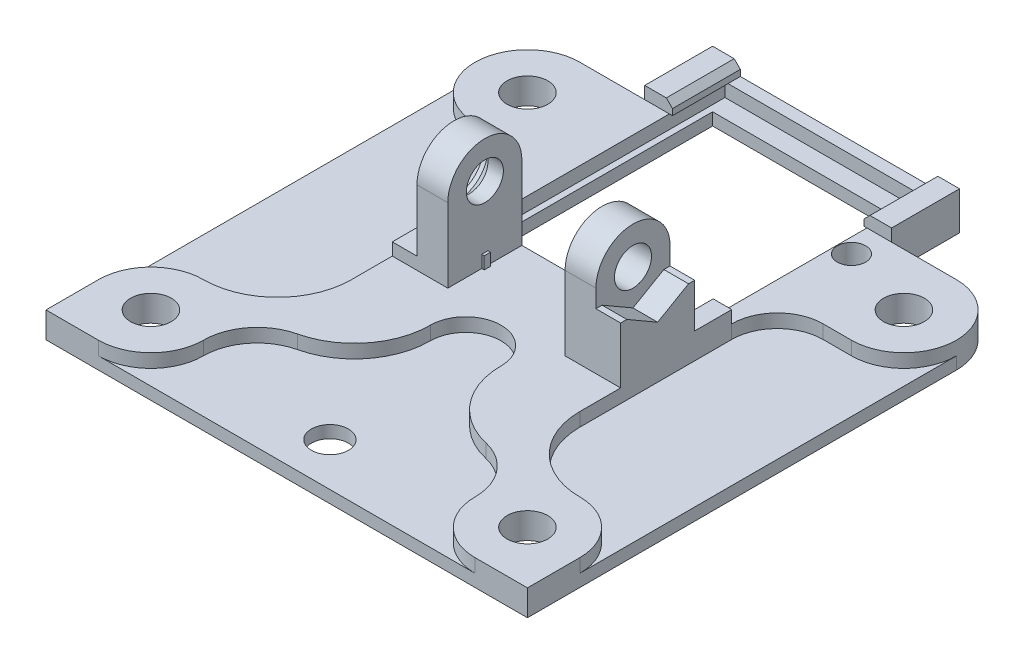
SolidWorks part; units mm, degrees
ref_plane "Front Plane" through (0, 0, 0) normal (0, 0, 1) x (1, 0, 0)
ref_plane "Top Plane" through (0, 0, 0) normal (0, 1, 0) x (1, 0, 0)
ref_plane "Right Plane" through (0, 0, 0) normal (1, 0, 0) x (0, 0, -1)
sketch "Sketch1" plane through (0, 0, 0) normal (0, 1, 0) x (1, 0, 0)
  line L0 (-19.5, 35.2) -> (-19.5, -19.5) construction
  line L1 (-19.5, 19.5) -> (19.5, 19.5)
  line L2 (-19.5, 19.5) -> (-19.5, -19.5)
  line L3 (-19.5, -19.5) -> (19.5, -19.5)
  line L4 (19.5, 19.5) -> (19.5, -19.5)
  line L5 (-19.5, 19.5) -> (19.5, -19.5) construction
  line L6 (-19.5, -19.5) -> (19.5, 19.5) construction
  line L7 (-19.5, -19.5) -> (19.5, -19.5) construction
  line L8 (0, -19.5) -> (0, 19.5) construction
  circle A0 centre (-15.25, -15.25) radius 1.65 construction
  circle A1 centre (15.25, -15.25) radius 1.65 construction
  circle A2 centre (9.2, 17.05) radius 1.15 construction
  circle A3 centre (15.25, 15.25) radius 1.65 construction
  circle A4 centre (-15.25, 15.25) radius 1.65 construction
  circle A5 centre (-15.25, -15.25) radius 1.65
  circle A6 centre (15.25, -15.25) radius 1.65
  circle A7 centre (9.2, 17.05) radius 1.15
  circle A8 centre (15.25, 15.25) radius 1.65
  circle A9 centre (-15.25, 15.25) radius 1.65
  circle A10 centre (-15.25, 15.25) radius 4.25
  circle A11 centre (15.25, 15.25) radius 4.25
  circle A12 centre (-15.25, -15.25) radius 4.25
  circle A13 centre (15.25, -15.25) radius 4.25
  circle A14 centre (0, -16) radius 1.5
  point P0 (0, 0)
  dimension "D1" = 3
  dimension "D2" = 3.5
extrude "Shape" add sketch "Sketch1" along normal blind 2.1 contours A13 L4 A11 L1 A10 L2 A12 L3 A7 | A10 A9 | A11 A8 | A13 A6 | A12 A5 | A12 L2 L3 | A13 L3 L4 region at (-0.0302, 0, -0.0333) region at (-12.3298, 0, -18.1702) region at (18.1702, 0, -18.1702) region at (-18.5507, 0, 18.5507) region at (-15.25, 0, 11.1202) region at (18.1702, 0, 18.1702) region at (18.5507, 0, 18.5507)
sketch "Sketch3" plane through (0, 2.1, 0) normal (0, 1, 0) x (1, 0, 0)
  line L0 (0, 19.5) -> (0, -19.5) construction
  line L1 (-15.25, 19.5) -> (15.25, 19.5) construction
  line L2 (-19.5, -19.5) -> (19.5, -19.5) construction
  line L3 (-19.5, 1.3) -> (19.5, 1.3) construction
  line L4 (-19.5, 15.25) -> (-19.5, -19.5) construction
  line L5 (19.5, 15.25) -> (19.5, -19.5) construction
  line L6 (4.75, 4.3) -> (7.25, 4.3)
  line L7 (-4.75, 4.3) -> (-7.25, 4.3)
  line L8 (-4.75, 4.3) -> (-4.75, -1.7)
  line L9 (-4.75, -1.7) -> (-7.25, -1.7)
  line L10 (-7.25, 4.3) -> (-7.25, -1.7)
  line L11 (-4.75, 4.3) -> (-7.25, -1.7) construction
  line L12 (-4.75, -1.7) -> (-7.25, 4.3) construction
  line L13 (4.75, 4.3) -> (4.75, -1.7)
  line L14 (4.75, -1.7) -> (7.25, -1.7)
  line L15 (7.25, 4.3) -> (7.25, -1.7)
  line L17 (7.25, 4.3) -> (9.25, 4.3)
  line L18 (7.25, 4.3) -> (7.25, -1.7)
  line L19 (7.25, -1.7) -> (9.25, -1.7)
  line L20 (9.25, 4.3) -> (9.25, -1.7)
  point P12 (-6, 1.3)
  dimension "D1" = 18.2
  dimension "D2" = 9.5
  dimension "D3" = 2.5
  dimension "D4" = 6
  dimension "D5" = 4.5
extrude "Supports" add sketch "Sketch3" along normal blind 9 contours L7 L10 L9 L8 | L15 L6 L13 L14 | L20 L17 L15 L19 region at (6, 2.1, -1.3) region at (8.25, 2.1, -1.3) region at (-6, 2.1, -1.3)
sketch "Sketch4" plane through (-7.25, 0, 0) normal (-1, 0, 0) x (0, 0, 1)
  line L0 (-1.3, 11.1) -> (-1.3, 2.1) construction
  line L2 (-4.3, 2.1) -> (1.7, 2.1) construction
  line L3 (1.7, 11.1) -> (1.7, 2.1) construction
  line L4 (-4.3, 11.1) -> (1.7, 11.1) construction
  circle A0 centre (-1.3, 8.1) radius 3
  circle A1 centre (-1.3, 8.1) radius 1.5
  line M2 (1.7, 2.1) -> (1.7, 11.1)
  line M4 (-4.3, 11.1) -> (-4.3, 2.1)
  line M11 (1.7, 11.1) -> (-4.3, 11.1)
  dimension "D1" = 3
extrude "Support cuts" cut sketch "Sketch4" against normal up to surface (16.5 mm away) contours A1 L0 | L0 A1 | A0 M11 M4 | A0 M2 M11 region at (-7.25, 10.4299, 1.0299) region at (-7.25, 10.4299, -3.6299) region at (-7.25, 8.1, -0.6634) region at (-7.25, 8.1, -1.9366) up to face at (9.25, 6.6, -1.3)
sketch "Sketch5" plane through (9.25, 0, 0) normal (1, 0, 0) x (0, 0, -1)
  line L0 (-1.2, 6.6566) -> (-1.7, 6.6566)
  line L1 (1.3, 5.2132) -> (3.8, 6.6566)
  line L2 (3.8, 6.6566) -> (3.8, 9.5434)
  line L3 (3.8, 9.5434) -> (1.3, 10.9868)
  line L4 (1.3, 10.9868) -> (-1.2, 9.5434)
  line L5 (-1.2, 9.5434) -> (-1.2, 6.6566)
  line L6 (-1.2, 6.6566) -> (1.3, 5.2132)
  line L7 (3.8, 6.6566) -> (4.3, 6.6566)
  line L9 (-1.7, 8.1) -> (-1.7, 2.1)
  line L10 (-1.7, 2.1) -> (4.3, 2.1)
  line L11 (4.3, 2.1) -> (4.3, 8.1)
  line L12 (-1.7, 8.1) -> (-1.7, 2.1)
  line L13 (-1.7, 2.1) -> (4.3, 2.1)
  line L14 (4.3, 2.1) -> (4.3, 8.1)
  circle A0 centre (1.3, 8.1) radius 2.5 construction
  circle A1 centre (1.3, 8.1) radius 1.5 construction
  arc A2 (4.3, 8.1) -> (-1.7, 8.1) centre (1.3, 8.1) ccw
  arc A3 (4.3, 8.1) -> (-1.7, 8.1) centre (1.3, 8.1) ccw
  circle M3 centre (1.3, 8.1) radius 1.5
  line M4 (-1.7, 8.1) -> (-1.7, 2.1)
  line M6 (4.3, 2.1) -> (4.3, 8.1)
  arc M7 (4.3, 8.1) -> (-1.7, 8.1) centre (1.3, 8.1) ccw
  dimension "D1" = 5
  dimension "D2" = 0
extrude "Nut holder" cut sketch "Sketch5" against normal blind 2 contours L5 L6 L1 L2 L3 L4 M3 | L2 L7 L0 L5 L4 L3 M6 M7 M4 region at (9.25, 6.7313, 1.45) region at (9.25, 8.1, 1.1236)
sketch "Sketch6" plane through (-7.25, 0, 0) normal (-1, 0, 0) x (0, 0, 1)
  circle A0 centre (-1.3, 8.1) radius 2.4
  dimension "D1" = 4.8
extrude "Screw cut" cut sketch "Sketch6" against normal blind 0.35
chamfer "Scew chamfer" distance 0.9 angle 45 1 edges at (-6.9, 8.1, 0.2)
sketch "Sketch7" plane through (4.75, 0, 0) normal (-1, 0, 0) x (0, 0, 1)
  line L0 (-1.3, 2.1) -> (-1.3, 11.1) construction
  line L1 (-4.3, 2.1) -> (1.7, 2.1) construction
  line L2 (-4.3, 2.1) -> (1.7, 2.1) construction
  line L3 (-1.05, 3.1) -> (-1.55, 3.1)
  line L4 (-1.05, 3.1) -> (-1.05, 2.1)
  line L5 (-1.05, 2.1) -> (-1.55, 2.1)
  line L6 (-1.55, 3.1) -> (-1.55, 2.1)
  line L7 (-1.05, 3.1) -> (-1.55, 2.1) construction
  line L8 (-1.05, 2.1) -> (-1.55, 3.1) construction
  arc A1 (1.7, 8.1) -> (-4.3, 8.1) centre (-1.3, 8.1) ccw construction
  point P4 (0, 0)
  point P5 (0, 0)
  point P7 (-1.3, 2.6)
  point P12 (0, 0)
  point P15 (-3.5, 11)
  point P16 (0, 0)
  dimension "D1" = 0.5
  dimension "D2" = 1
extrude "Angle fix 1" add sketch "Sketch7" along normal blind 0.2
sketch "Sketch8" plane through (-4.75, 0, 0) normal (1, 0, 0) x (0, 0, -1)
  line L4 (1.55, 2.1) -> (1.55, 3.1)
  line L5 (1.05, 2.1) -> (1.55, 2.1)
  line L6 (1.05, 3.1) -> (1.05, 2.1)
  line L7 (1.55, 3.1) -> (1.05, 3.1)
  line L8 (1.55, 2.1) -> (1.55, 3.1)
  line L9 (1.05, 2.1) -> (1.55, 2.1)
  line L10 (1.05, 3.1) -> (1.05, 2.1)
  line L11 (1.55, 3.1) -> (1.05, 3.1)
  dimension "D1" = 0
extrude "Angle fix 2" add sketch "Sketch8" along normal blind 0.2
sketch "Sketch9" plane through (0, 2.1, 0) normal (0, 1, 0) x (1, 0, 0)
  line L0 (8, 4.5) -> (8, 24) construction
  line L1 (8, 24) -> (-8, 24) construction
  line L2 (-8, 24) -> (-8, 4.5) construction
  line L3 (8, 4.5) -> (8, 24)
  line L4 (8, 24) -> (-8, 24)
  line L5 (-8, 24) -> (-8, 4.5)
  line L6 (-15.25, 19.5) -> (15.25, 19.5) construction
  line L7 (-15.25, 19.5) -> (15.25, 19.5)
  line L8 (-8, 24) -> (8, 19.5) construction
  line L9 (-8, 24) -> (8, 24)
  line L14 (10, 25) -> (-10, 25)
  line L15 (10, 25) -> (10, 18.5)
  line L16 (10, 18.5) -> (-10, 18.5)
  line L17 (-10, 25) -> (-10, 18.5)
  line L18 (10, 25) -> (-10, 18.5) construction
  line L19 (10, 18.5) -> (-10, 25) construction
  point P10 (0, 21.75)
  line M5 (15.25, 19.5) -> (-15.25, 19.5)
  dimension "D1" = 1
  dimension "D2" = 2
extrude "Datalogger front" add sketch "Sketch9" against normal up to surface (2.1 mm away) contours L4 L5 L3 M5 | L14 L17 L5 L4 L3 L7 L15 M5 region at (0, 2.1, -21.75) region at (8.2074, 2.1, -21.75) up to face at (0, 0, 17.5)
sketch "Sketch10" plane through (0, 0, -25) normal (0, 0, -1) x (-1, 0, 0)
  line L1 (-8, 2.1) -> (8, 2.1)
  line L2 (-8, 2.1) -> (-8, 1)
  line L3 (-8, 1) -> (8, 1)
  line L4 (8, 2.1) -> (8, 1)
  line L6 (-8, 1) -> (8, 1) construction
  line L8 (8, 2.1) -> (8, 1) construction
extrude "Datalogger main cut" cut sketch "Sketch10" against normal offset from surface (20.7 mm away) 0.2 offset beyond the face yes
sketch "Sketch11" plane through (0, 1, 0) normal (0, 1, 0) x (1, 0, 0)
  line L6 (-7.5, 22.5) -> (7.5, 22.5)
  line L9 (8, 25) -> (-8, 25) construction
  line L12 (-7.5, 4.8) -> (7.5, 4.8)
  line L13 (7.5, 4.8) -> (7.5, 24.5)
  line L14 (7.5, 24.5) -> (-7.5, 24.5)
  line L15 (7.5, 24.5) -> (-7.5, 24.5)
  line L17 (-7.5, 24.5) -> (-7.5, 4.8)
  line L18 (-7.5, 4.8) -> (7.5, 4.8)
  line L19 (7.5, 4.8) -> (7.5, 24.5)
  line L23 (-7.5, 24.5) -> (-7.5, 4.8)
  point P5 (-7.5, 22.5)
  point P6 (7.5, 22.5)
  dimension "D2" = 2.5
  dimension "D1" = 0.5
extrude "Datalogger bottom cut" cut sketch "Sketch11" against normal up to next contours L23 L18 L19 region at (0, 1, -13.65)
sketch "Sketch12" plane through (0, 1, 0) normal (0, 1, 0) x (1, 0, 0)
  line L1 (-8, 25) -> (8, 25)
  line L2 (-8, 25) -> (-8, 24)
  line L3 (-8, 24) -> (8, 24)
  line L4 (8, 25) -> (8, 24)
  point P5 (0, 0)
  point P6 (0, 0)
  point P7 (0, 0)
  dimension "D1" = 1
extrude "Datalogger front retainer" add sketch "Sketch12" along normal up to surface (1.1 mm away) up to face at (0.1333, 2.1, -6.6887)
sketch "Sketch13" plane through (0, 2.1, 0) normal (0, 1, 0) x (1, 0, 0)
  line L1 (-8, 4.3) -> (-9.25, 4.3)
  line L2 (-8, 4.3) -> (-8, 7.3)
  line L3 (-8, 7.3) -> (-9.25, 7.3)
  line L4 (-9.25, 4.3) -> (-9.25, 7.3)
  line L5 (-8, 7.3) -> (-7.75, 7.3)
  line L6 (-8, 7.3) -> (-8, 4.3)
  line L7 (-8, 4.3) -> (-7.75, 4.3)
  line L8 (-7.75, 7.3) -> (-7.75, 4.3)
  line L9 (0, 7.608) -> (0, -4.6396) construction
  line L10 (9.25, 4.3) -> (9.25, 7.3)
  line L11 (8, 7.3) -> (9.25, 7.3)
  line L12 (8, 7.3) -> (7.75, 7.3)
  line L13 (7.75, 7.3) -> (7.75, 4.3)
  line L14 (8, 4.3) -> (7.75, 4.3)
  line L15 (8, 4.3) -> (9.25, 4.3)
  line L16 (-7.25, 4.3) -> (-7.25, -1.7) construction
  line L17 (-9.25, 4.3) -> (-7.25, 4.3)
  line L18 (-9.25, 4.3) -> (-9.25, -1.7)
  line L19 (-9.25, -1.7) -> (-7.25, -1.7)
  line L20 (-7.25, 4.3) -> (-7.25, -1.7)
  line L21 (-4.75, -1.7) -> (-7.25, -1.7) construction
  line L22 (9.25, 4.3) -> (9.25, -1.7) construction
  line M8 (8, 24) -> (8, 4.3)
  line M9 (8, 4.3) -> (9.25, 4.3)
  line M25 (-7.25, 4.3) -> (-8, 4.3)
  line M26 (-8, 4.3) -> (-8, 24)
  line M52 (-7.25, -1.7) -> (-7.25, 4.3)
  dimension "D2" = 3
  dimension "D3" = 0.25
extrude "Datalogger rear retainers" add sketch "Sketch13" along normal blind 1 contours L4 L3 M25 M26 | L8 L5 L7 M26 | L11 L10 M8 M9 | L14 L12 L13 M8 | L18 L19 L1 M52 M25 region at (-8.25, 2.1, -1.3) region at (-8.625, 2.1, -5.8) region at (-7.875, 2.1, -5.8) region at (8.625, 2.1, -5.8) region at (7.875, 2.1, -5.8)
sketch "Sketch14" plane through (0, 2.1, 0) normal (0, 1, 0) x (1, 0, 0)
  line L0 (-15.25, 19.5) -> (-10, 19.5) construction
  line L1 (-10, 25) -> (-7.75, 25)
  line L2 (-10, 25) -> (-10, 19.5)
  line L3 (-10, 19.5) -> (-7.75, 19.5)
  line L4 (-7.75, 25) -> (-7.75, 19.5)
  line L5 (-8, 4.3) -> (-8, 24) construction
  line L8 (0, 25) -> (0, -19.5) construction
  line L9 (10, 25) -> (-10, 25) construction
  line L10 (-19.5, -19.5) -> (19.5, -19.5) construction
  line L11 (10, 25) -> (10, 19.5)
  line L12 (10, 25) -> (7.75, 25)
  line L13 (7.75, 25) -> (7.75, 19.5)
  line L14 (10, 19.5) -> (7.75, 19.5)
  line M43 (10, 19.5) -> (10, 25)
  line M45 (10, 25) -> (-10, 25)
  line M46 (8, 24) -> (8, 7.3)
  line M68 (-8, 7.3) -> (-8, 24)
  line M71 (-10, 25) -> (-10, 19.5)
  line M161 (-8, 24) -> (8, 24)
  dimension "D1" = 0.25
extrude "Datalogger side retainers" add sketch "Sketch14" along normal up to surface (1 mm away) contours M45 M161 M46 M43 | M71 M68 M161 | L4 L3 M161 M68 | L14 L13 M46 M161 region at (-8.975, 2.1, -22.3) region at (-7.875, 2.1, -21.75) region at (8.975, 2.1, -22.3) region at (7.875, 2.1, -21.75) up to face at (-8.0833, 3.1, -3.3)
sketch "Sketch15" plane through (0, 0, -25) normal (0, 0, -1) x (-1, 0, 0)
  line L0 (-7.75, 2.6) -> (-8.25, 3.1)
  line L1 (-7.75, 3.1) -> (-7.75, 2.1) construction
  line L3 (-8.25, 3.1) -> (-7.75, 3.1)
  line L4 (-7.75, 3.1) -> (-7.75, 2.6)
  line L5 (0, 0) -> (0, 2.1) construction
  line L6 (-7.75, 2.1) -> (7.75, 2.1) construction
  line L7 (8.25, 3.1) -> (7.75, 3.1)
  line L8 (7.75, 3.1) -> (7.75, 2.6)
  line L9 (7.75, 2.6) -> (8.25, 3.1)
  point P16 (0, 0)
  dimension "D1" = 45
extrude "Datalogger side retainer clips" cut sketch "Sketch15" against normal up to next
sketch "Sketch16" plane through (0, 2.1, 0) normal (0, 1, 0) x (1, 0, 0)
  line L0 (-19.5, 15.25) -> (-19.5, -19.5) construction
  line L1 (-15.25, 11) -> (-15.25, -11) construction
  line L2 (0, -2.1397) -> (-2.8603, -2.1397) construction
  line L3 (0, 25) -> (0, -19.5) construction
  line L4 (7.75, 25) -> (-7.75, 25) construction
  line L5 (-19.5, -19.5) -> (19.5, -19.5) construction
  line L6 (-15.25, -11) -> (0, -11) construction
  line L7 (-11, -15.25) -> (0, -15.25) construction
  line L8 (-2.8603, 25) -> (-2.8603, -19.5) construction
  line L10 (-9.25, 7.3) -> (-9.25, 19.5) construction
  line L11 (-10, 19.5) -> (-8, 19.5) construction
  line L12 (-19.5, 15.25) -> (-19.5, -15.25)
  line L13 (-9.25, -1.7) -> (-9.25, -11) construction
  line L14 (-9.25, -5) -> (0, -5) construction
  line L15 (-15.25, 11) -> (-9.25, 11) construction
  line L16 (-9.25, 7.3) -> (-9.25, -5)
  line L18 (9.25, 7.3) -> (9.25, -5)
  line L19 (-15.25, -19.5) -> (15.25, -19.5)
  line L20 (15.25, 11) -> (12.95, 11)
  line L22 (-15.25, 11) -> (-12.95, 11)
  circle A0 centre (-15.25, 15.25) radius 4.25
  circle A1 centre (-15.25, -15.25) radius 4.25
  arc A2 (-15.25, 19.5) -> (-19.5, 15.25) centre (-15.25, 15.25) ccw construction
  arc A3 (-9.25, 7.3) -> (-12.95, 11) centre (-12.95, 7.3) ccw
  arc A4 (-15.25, -11) -> (-9.25, -5) centre (-15.25, -5) ccw
  arc A5 (-11, -15.25) -> (-7.625, -11) centre (-6.6366, -15.25) cw
  arc A6 (-7.625, -11) -> (-2.8603, -5) centre (-9.0204, -5) ccw
  arc A7 (-2.8603, -5) -> (2.8603, -5) centre (0, -5) cw
  arc A8 (7.625, -11) -> (2.8603, -5) centre (9.0204, -5) cw
  arc A9 (11, -15.25) -> (7.625, -11) centre (6.6366, -15.25) ccw
  circle A10 centre (15.25, -15.25) radius 4.25
  arc A11 (15.25, -11) -> (9.25, -5) centre (15.25, -5) cw
  arc A12 (9.25, 7.3) -> (12.95, 11) centre (12.95, 7.3) cw
  circle A13 centre (15.25, 15.25) radius 4.25
  point P25 (0, 0)
  line M39 (-19.5, 15.25) -> (-19.5, -19.5)
  line M40 (-19.5, -19.5) -> (19.5, -19.5)
  line M41 (19.5, -19.5) -> (19.5, 15.25)
  circle M45 centre (0, -16) radius 1.5
extrude "Weight cut" cut sketch "Sketch16" against normal offset from surface (1.1 mm away) 1 contours A1 A0 M39 | A10 A9 A8 A7 A6 A5 A1 M40 M45 | A13 L18 A10 M41 region at (-14.7085, 2.1, -0.201) region at (0, 2.1, 13.4582) region at (14.7085, 2.1, -0.201) up to face at (15.25, 0, 16.9)
